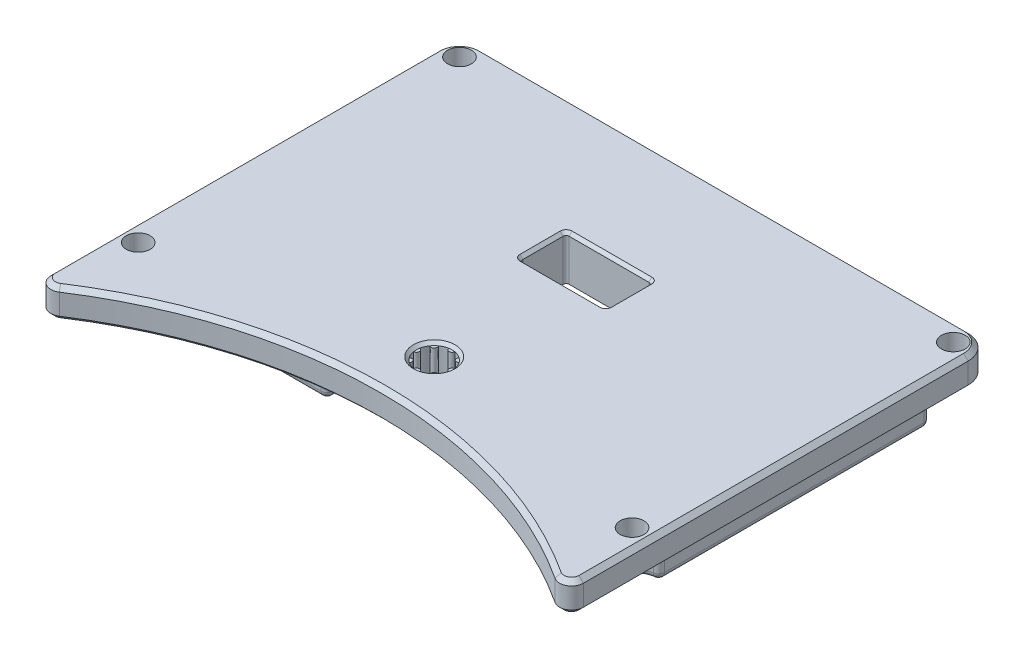
SolidWorks part; units mm, degrees
ref_plane "Front Plane" through (0, 0, 0) normal (0, 0, 1) x (1, 0, 0)
ref_plane "Top Plane" through (0, 0, 0) normal (0, 1, 0) x (1, 0, 0)
ref_plane "Right Plane" through (0, 0, 0) normal (1, 0, 0) x (0, 0, -1)
sketch "Sketch1" plane through (0, 0, 0) normal (0, 1, 0) x (1, 0, 0)
  line L5 (-45, -39.4213) -> (-45, 25.25) construction
  line L10 (-41, 29.25) -> (40.5, 29.25) construction
  line L11 (44.5, 25.25) -> (44.5, -39.4213) construction
  line L20 (-45, 25.25) -> (-45, -39.4213)
  line L21 (40.5, 29.25) -> (-41, 29.25)
  line L22 (44.5, -39.4213) -> (44.5, 25.25)
  arc A0 (-41, 29.25) -> (-45, 25.25) centre (-41, 25.25) ccw construction
  arc A1 (-45, -39.4213) -> (-41.9101, -41.0982) centre (-43, -39.4213) ccw construction
  arc A2 (44.5, 25.25) -> (40.5, 29.25) centre (40.5, 25.25) ccw construction
  arc A3 (41.4101, -41.0982) -> (44.5, -39.4213) centre (42.5, -39.4213) ccw construction
  arc A4 (41.4101, -41.0982) -> (-41.9101, -41.0982) centre (-0.25, -105.2) ccw construction
  arc A20 (41.4101, -41.0982) -> (-41.9101, -41.0982) centre (-0.25, -105.2) ccw
  arc A32 (-45, -39.4213) -> (-41.9101, -41.0982) centre (-43, -39.4213) ccw
  arc A34 (41.4101, -41.0982) -> (44.5, -39.4213) centre (42.5, -39.4213) ccw
  arc A100 (-41, 29.25) -> (-45, 25.25) centre (-41, 25.25) ccw
  arc A121 (44.5, 25.25) -> (40.5, 29.25) centre (40.5, 25.25) ccw
extrude "Boss-Extrude1" add sketch "Sketch1" along normal blind 5
sketch "Sketch2" plane through (0, 5, 0) normal (0, 1, 0) x (1, 0, 0)
  circle A0 centre (41.25, 26) radius 1.25
  circle A2 centre (-41.75, 26) radius 1.25
  circle A4 centre (41.25, -28) radius 1.25
  circle A5 centre (-41.75, 26) radius 1.2784 construction
  circle A6 centre (-41.75, -28) radius 1.25
  circle A7 centre (-41.75, -28) radius 1.2784 construction
  circle A10 centre (41.25, 26) radius 1.2784 construction
  circle A11 centre (41.25, -28) radius 1.2784 construction
  dimension "D1" = 2.5
extrude "Cut-Extrude1" cut sketch "Sketch2" against normal through all both and the other way through all
sketch "Sketch3" plane through (0, 5, 0) normal (0, 1, 0) x (1, 0, 0)
  circle A0 centre (-41.75, 26) radius 2
  circle A1 centre (41.25, 26) radius 2
  circle A2 centre (41.25, -28) radius 2
  circle A3 centre (-41.75, -28) radius 2
  circle A4 centre (-41.75, 26) radius 1.25 construction
  circle A5 centre (41.25, 26) radius 1.25 construction
  circle A6 centre (41.25, -28) radius 1.25 construction
  circle A7 centre (-41.75, -28) radius 1.25 construction
  dimension "D1" = 4
extrude "Cut-Extrude2" cut sketch "Sketch3" against normal blind 3
sketch "Sketch4" plane through (0, 5, 0) normal (0, 1, 0) x (1, 0, 0)
  circle A3 centre (-0.25, -19.75) radius 3
  dimension "D2" = 6
extrude "Cut-Extrude3" cut sketch "Sketch4" against normal through all both and the other way through all
chamfer "Chamfer3" distance 0.75 angle 45 20 edges at (41.25, 0, -24.75) (-41.75, 0, 29.25) (41.25, 0, 29.25) (-41.75, 0, -24.75) (44.5, 0, 7.0856) (-0.25, 0, -29.25) (-43.8284, 0, -28.0784) (-45, 0, 7.0856) (-0.25, 0, 28.75) (-45, 5, 7.0856) (-43.8284, 5, -28.0784) (-0.25, 5, 28.75) (-0.25, 5, -29.25) (44.5, 5, 7.0856) (43.3284, 0, -28.0784) (43.3284, 5, -28.0784) (-43.954, 0, 41.1791) (43.454, 0, 41.1791) (-43.954, 5, 41.1791) (43.454, 5, 41.1791)
chamfer "Chamfer4" distance 0.5 angle 45 2 edges at (-0.25, 0, 22.75) (-0.25, 5, 22.75)
ref_plane "Plane1" through (0, 0.5, 0) normal (0, -1, 0) x (-1, 0, 0)
ref_plane "Plane2" through (0, 4.5, 0) normal (0, 1, 0) x (1, 0, 0)
sketch "Sketch5" plane through (0, 0.5, 0) normal (0, -1, 0) x (-1, 0, 0)
  line L0 (-2.75, -19.75) -> (-1.8713, -17.6287) construction
  line L1 (-1.8713, -17.6287) -> (0.25, -16.75) construction
  line L2 (0.25, -16.75) -> (2.3713, -17.6287) construction
  line L3 (2.3713, -17.6287) -> (3.25, -19.75) construction
  line L4 (3.25, -19.75) -> (2.3713, -21.8713) construction
  line L5 (2.3713, -21.8713) -> (0.25, -22.75) construction
  line L6 (-1.8713, -21.8713) -> (0.25, -22.75) construction
  line L7 (-2.75, -19.75) -> (-1.8713, -21.8713) construction
  circle A0 centre (0.25, -16.75) radius 0.5
  circle A1 centre (0.25, -19.75) radius 3 construction
  circle A2 centre (-2.75, -19.75) radius 0.5
  circle A3 centre (0.25, -22.75) radius 0.5
  circle A4 centre (3.25, -19.75) radius 0.5
  circle A5 centre (2.3713, -17.6287) radius 0.5
  circle A6 centre (-1.8713, -17.6287) radius 0.5
  circle A7 centre (-1.8713, -21.8713) radius 0.5
  circle A8 centre (2.3713, -21.8713) radius 0.5
  dimension "D1" = 1
extrude "Boss-Extrude2" add sketch "Sketch5" against normal up to surface (4 mm away) up to plane "Plane2"
sketch "Sketch8" plane through (0, 5, 0) normal (0, 1, 0) x (1, 0, 0)
  line L0 (-6.45, 8.625) -> (-6.45, 2.875) construction
  line L1 (-6.45, 2.875) -> (5.95, 2.875) construction
  line L2 (-6.45, 2.875) -> (-6.45, 8.625) construction
  line L3 (-6.45, 8.625) -> (5.95, 8.625) construction
  line L4 (5.95, 2.875) -> (5.95, 8.625) construction
  line L5 (-6.45, 2.875) -> (5.95, 8.625) construction
  line L6 (-6.45, 8.625) -> (5.95, 2.875) construction
  line L7 (5.95, 8.625) -> (-6.45, 8.625) construction
  line L8 (-7.45, 1.875) -> (-7.45, 9.625)
  line L9 (-7.45, 9.625) -> (6.95, 9.625)
  line L10 (6.95, 1.875) -> (6.95, 9.625)
  line L11 (-7.45, 1.875) -> (6.95, 1.875)
  line L14 (-6.45, 8.625) -> (-6.45, 4.675) construction
  point P0 (-0.25, 5.75)
  dimension "D1" = 1
extrude "Cut-Extrude4" cut sketch "Sketch8" against normal through all both and the other way through all
fillet "Fillet1" radius 0.5 4 edges at (6.95, 2.5, -1.875) (-7.45, 2.5, -1.875) (-7.45, 2.5, -9.625) (6.95, 2.5, -9.625)
sketch "Sketch11" plane through (0, 0, 0) normal (0, -1, 0) x (1, 0, 0)
  line L0 (6.45, -9.625) -> (-6.95, -9.625) construction
  line L1 (-7.45, -9.125) -> (-7.45, -2.375) construction
  line L2 (-6.95, -1.875) -> (6.45, -1.875) construction
  line L3 (6.95, -2.375) -> (6.95, -9.125) construction
  line L4 (6.45, -9.625) -> (-6.95, -9.625)
  line L5 (-7.45, -9.125) -> (-7.45, -2.375)
  line L6 (-6.95, -1.875) -> (6.45, -1.875)
  line L7 (6.95, -2.375) -> (6.95, -9.125)
  line L8 (6.45, -11.625) -> (-6.95, -11.625)
  line L9 (-9.45, -9.125) -> (-9.45, -2.375)
  line L10 (-6.95, 0.125) -> (6.45, 0.125)
  line L11 (8.95, -2.375) -> (8.95, -9.125)
  arc A0 (6.45, -9.625) -> (6.95, -9.125) centre (6.45, -9.125) ccw construction
  arc A1 (-7.45, -9.125) -> (-6.95, -9.625) centre (-6.95, -9.125) ccw construction
  arc A2 (-6.95, -1.875) -> (-7.45, -2.375) centre (-6.95, -2.375) ccw construction
  arc A3 (6.95, -2.375) -> (6.45, -1.875) centre (6.45, -2.375) ccw construction
  arc A4 (6.45, -9.625) -> (6.95, -9.125) centre (6.45, -9.125) ccw
  arc A5 (-7.45, -9.125) -> (-6.95, -9.625) centre (-6.95, -9.125) ccw
  arc A6 (-6.95, -1.875) -> (-7.45, -2.375) centre (-6.95, -2.375) ccw
  arc A7 (6.95, -2.375) -> (6.45, -1.875) centre (6.45, -2.375) ccw
  arc A8 (-9.45, -9.125) -> (-6.95, -11.625) centre (-6.95, -9.125) ccw
  arc A9 (-6.95, 0.125) -> (-9.45, -2.375) centre (-6.95, -2.375) ccw
  arc A10 (8.95, -2.375) -> (6.45, 0.125) centre (6.45, -2.375) ccw
  arc A11 (6.45, -11.625) -> (8.95, -9.125) centre (6.45, -9.125) ccw
  dimension "D1" = 2
extrude "Boss-Extrude4" add sketch "Sketch11" along normal blind 2.5
sketch "Sketch9" plane through (0, 0, 0) normal (0, -1, 0) x (1, 0, 0)
  line L0 (38.25, -27.25) -> (-38.75, -27.25) construction
  line L1 (42.5, 25) -> (42.5, -23) construction
  line L2 (-39.0114, 26.25) -> (38.5114, 26.25) construction
  line L3 (-43, -23) -> (-43, 25) construction
  line L4 (38.25, -27.25) -> (-38.75, -27.25)
  line L5 (42.5, 25) -> (42.5, -23)
  line L6 (-39.0114, 26.25) -> (38.5114, 26.25)
  line L7 (-43, -23) -> (-43, 25)
  arc A0 (-38.75, -27.25) -> (-43, -23) centre (-41.75, -26) ccw construction
  arc A1 (42.5, -23) -> (38.25, -27.25) centre (41.25, -26) ccw construction
  arc A2 (38.5114, 26.25) -> (42.5, 25) centre (41.25, 28) ccw construction
  arc A3 (-43, 25) -> (-39.0114, 26.25) centre (-41.75, 28) ccw construction
  arc A4 (-38.75, -27.25) -> (-43, -23) centre (-41.75, -26) ccw
  arc A5 (42.5, -23) -> (38.25, -27.25) centre (41.25, -26) ccw
  arc A6 (38.5114, 26.25) -> (42.5, 25) centre (41.25, 28) ccw
  arc A7 (-43, 25) -> (-39.0114, 26.25) centre (-41.75, 28) ccw
sketch "Sketch10" plane through (0, 0, 0) normal (0, -1, 0) x (1, 0, 0)
  line L4 (-35.75, -24.25) -> (35.25, -24.25)
  line L5 (39.5, -20) -> (39.5, 22)
  line L6 (37.188, 23.25) -> (-37.688, 23.25) construction
  line L7 (-40, 22) -> (-40, -20)
  line L8 (-37.5074, -26.25) -> (37.0074, -26.25)
  line L9 (-42, 23.7574) -> (-42, -21.7574)
  line L10 (38.0096, 25.25) -> (-38.5096, 25.25)
  line L11 (41.5, -21.7574) -> (41.5, 23.7574)
  line L12 (-37.5074, -26.25) -> (37.0074, -26.25)
  line L13 (-42, 23.7574) -> (-42, -21.7574)
  line L14 (38.0096, 25.25) -> (-38.5096, 25.25) construction
  line L15 (41.5, -21.7574) -> (41.5, 23.7574)
  line L16 (37.188, 23.25) -> (12.25, 23.25)
  line L17 (12.25, 23.25) -> (12.25, 25.25)
  line L18 (12.25, 25.25) -> (38.0096, 25.25)
  line L19 (-37.688, 23.25) -> (-12.75, 23.25)
  line L20 (-12.75, 23.25) -> (-12.75, 25.25)
  line L21 (-12.75, 25.25) -> (-38.5096, 25.25)
  line L22 (-12.75, 25.25) -> (12.25, 25.25) construction
  circle A0 centre (-0.25, 19.75) radius 3.5 construction
  circle A1 centre (-0.25, 19.75) radius 3.5 construction
  arc A4 (39.5, -20) -> (35.25, -24.25) centre (41.25, -26) ccw
  arc A5 (37.188, 23.25) -> (39.5, 22) centre (41.25, 28) ccw
  arc A6 (-40, 22) -> (-37.688, 23.25) centre (-41.75, 28) ccw
  arc A7 (-35.75, -24.25) -> (-40, -20) centre (-41.75, -26) ccw
  arc A8 (-37.5074, -26.25) -> (-42, -21.7574) centre (-41.75, -26) ccw
  arc A9 (-42, 23.7574) -> (-38.5096, 25.25) centre (-41.75, 28) ccw
  arc A10 (38.0096, 25.25) -> (41.5, 23.7574) centre (41.25, 28) ccw
  arc A11 (41.5, -21.7574) -> (37.0074, -26.25) centre (41.25, -26) ccw
  arc A12 (-37.5074, -26.25) -> (-42, -21.7574) centre (-41.75, -26) ccw
  arc A13 (-42, 23.7574) -> (-38.5096, 25.25) centre (-41.75, 28) ccw
  arc A14 (38.0096, 25.25) -> (41.5, 23.7574) centre (41.25, 28) ccw
  arc A15 (41.5, -21.7574) -> (37.0074, -26.25) centre (41.25, -26) ccw
  point P13 (-0.25, 25.25)
  dimension "D3" = 25
  dimension "D1" = 1
  dimension "D2" = 2
extrude "Boss-Extrude3" add sketch "Sketch10" along normal blind 5
fillet "Fillet2" radius 5 7 edges at (24.719, 0, 23.25) (39.5, 0, 1) (36.8306, 0, -21.5806) (-0.25, 0, -24.25) (-37.3306, 0, -21.5806) (-40, 0, 1) (-25.219, 0, 23.25)
fillet "Fillet4" radius 1 8 edges at (-8.7178, 0, -10.8928) (-9.45, 0, -5.75) (-8.7178, 0, -0.6072) (-0.25, 0, 0.125) (8.2178, 0, -0.6072) (8.95, 0, -5.75) (8.2178, 0, -10.8928) (-0.25, 0, -11.625)
fillet "Fillet3" radius 1 21 edges at (25.1298, -5, 25.25) (38.0096, -2.5, 25.25) (39.5789, -5, 24.0923) (41.5, -2.5, 23.7574) (37.0074, -2.5, -26.25) (41.5, -2.5, -21.7574) (41.5, -5, 1) (38.2448, -5, -22.9948) (-38.5096, -2.5, 25.25) (-40.0789, -5, 24.0923) (-42, -2.5, 23.7574) (-42, -5, 1) (-42, -2.5, -21.7574) (-38.7448, -5, -22.9948) (-37.5074, -2.5, -26.25) (-0.25, -5, -26.25) (-12.75, -5, 24.25) (-25.6298, -5, 25.25) (-12.75, -2.5, 25.25) (12.25, -2.5, 25.25) (12.25, -5, 24.25)
chamfer "Chamfer6" distance 0.5 angle 45 8 edges at (-0.25, 5, -9.625) (-7.3036, 5, -9.4786) (6.8036, 5, -9.4786) (-7.45, 5, -5.75) (6.95, 5, -5.75) (-7.3036, 5, -2.0214) (6.8036, 5, -2.0214) (-0.25, 5, -1.875)
sketch "Sketch14" [suppressed] plane through (0, 0, 0) normal (0, -1, 0) x (1, 0, 0)
  line L0 (-35, 18.25) -> (-35, -19.25)
  line L1 (-35, -19.25) -> (34.5, -19.25)
  line L2 (34.5, -19.25) -> (34.5, 18.25)
  line L3 (-12.75, 18.25) -> (-35, 18.25)
  line L4 (34.5, 18.25) -> (12.25, 18.25)
  line L5 (-12.75, 18.25) -> (-5.7747, 18.25)
  line L6 (-5.7747, 18.25) -> (-5.7747, 2.6291)
  line L7 (-5.7747, 2.6291) -> (-11.9541, 2.6291)
  line L8 (-11.9541, 2.6291) -> (-11.9541, -14.1291)
  line L9 (-11.9541, -14.1291) -> (11.4541, -14.1291)
  line L10 (11.4541, -14.1291) -> (11.4541, 2.6291)
  line L11 (11.4541, 2.6291) -> (5.2747, 2.6291)
  line L12 (5.2747, 2.6291) -> (5.2747, 18.25)
  line L13 (5.2747, 18.25) -> (12.25, 18.25)
  line L14 (5.2747, 2.6291) -> (-5.7747, 2.6291) construction
  line L15 (-10.45, -5.75) -> (-11.9541, -5.75) construction
  line L16 (-10.45, -9.125) -> (-10.45, -2.375) construction
  line L17 (-0.25, -12.625) -> (-0.25, -14.1291) construction
  line L19 (-6.95, 1.125) -> (6.45, 1.125) construction
  line L20 (6.45, -12.625) -> (-6.95, -12.625) construction
  point P3 (-0.25, 2.6291)
  point P24 (-0.25, -14.1291)
  point P37 (-0.25, 1.125)
extrude "Cut-Extrude5" [suppressed] cut sketch "Sketch14" against normal through all both and the other way through all
fillet "Fillet5" [suppressed] radius 3
chamfer "Chamfer7" [suppressed] distance 1 angle 45
